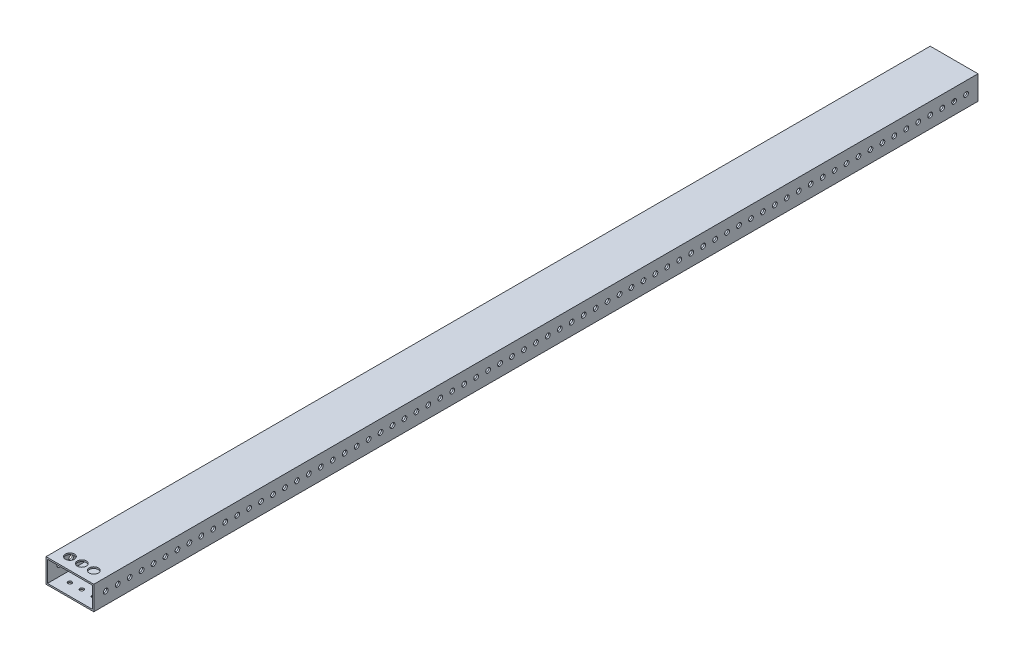
SolidWorks part; units mm, degrees
ref_plane "Front Plane" through (0, 0, 0) normal (0, 0, 1) x (1, 0, 0)
ref_plane "Top Plane" through (0, 0, 0) normal (0, 1, 0) x (1, 0, 0)
ref_plane "Right Plane" through (0, 0, 0) normal (1, 0, 0) x (0, 0, -1)
sketch "Sketch1" plane through (0, 0, 0) normal (0, 0, 1) x (1, 0, 0)
  line L0 (-23.8125, 11.1125) -> (23.8125, 11.1125)
  line L1 (-25.4, -12.7) -> (25.4, -12.7)
  line L2 (-25.4, -12.7) -> (-25.4, 12.7)
  line L3 (-25.4, 12.7) -> (25.4, 12.7)
  line L4 (25.4, -12.7) -> (25.4, 12.7)
  line L5 (-25.4, -12.7) -> (25.4, 12.7) construction
  line L6 (-25.4, 12.7) -> (25.4, -12.7) construction
  line L7 (23.8125, -11.1125) -> (23.8125, 11.1125)
  line L8 (-23.8125, -11.1125) -> (23.8125, -11.1125)
  line L9 (-23.8125, -11.1125) -> (-23.8125, 11.1125)
  point P0 (0, 0)
  dimension "D1" = 50.8
  dimension "D2" = 25.4
  dimension "D3" = 1.5875
extrude "Boss-Extrude1" add sketch "Sketch1" along normal mid plane 939.8
sketch "Sketch2" plane through (25.4, 0, 0) normal (1, 0, 0) x (0, 0, -1)
  line L0 (469.9, -12.7) -> (469.9, 12.7) construction
  line L1 (-469.9, -12.7) -> (-469.9, 12.7) construction
  line L2 (-469.9, 12.7) -> (469.9, 12.7) construction
  line L3 (-469.9, -12.7) -> (469.9, -12.7) construction
  circle A0 centre (457.2, 0) radius 2.54
  circle A1 centre (444.5, 0) radius 2.54
  circle A2 centre (431.8, 0) radius 2.54
  circle A3 centre (419.1, 0) radius 2.54
  circle A4 centre (406.4, 0) radius 2.54
  circle A5 centre (393.7, 0) radius 2.54
  circle A6 centre (381, 0) radius 2.54
  circle A7 centre (368.3, 0) radius 2.54
  circle A8 centre (355.6, 0) radius 2.54
  circle A9 centre (342.9, 0) radius 2.54
  circle A10 centre (330.2, 0) radius 2.54
  circle A11 centre (317.5, 0) radius 2.54
  circle A12 centre (304.8, 0) radius 2.54
  circle A13 centre (292.1, 0) radius 2.54
  circle A14 centre (279.4, 0) radius 2.54
  circle A15 centre (266.7, 0) radius 2.54
  circle A16 centre (254, 0) radius 2.54
  circle A17 centre (241.3, 0) radius 2.54
  circle A18 centre (228.6, 0) radius 2.54
  circle A19 centre (215.9, 0) radius 2.54
  circle A20 centre (203.2, 0) radius 2.54
  circle A21 centre (190.5, 0) radius 2.54
  circle A22 centre (177.8, 0) radius 2.54
  circle A23 centre (165.1, 0) radius 2.54
  circle A24 centre (152.4, 0) radius 2.54
  circle A25 centre (139.7, 0) radius 2.54
  circle A26 centre (127, 0) radius 2.54
  circle A27 centre (114.3, 0) radius 2.54
  circle A28 centre (101.6, 0) radius 2.54
  circle A29 centre (88.9, 0) radius 2.54
  circle A30 centre (76.2, 0) radius 2.54
  circle A31 centre (63.5, 0) radius 2.54
  circle A32 centre (50.8, 0) radius 2.54
  circle A33 centre (38.1, 0) radius 2.54
  circle A34 centre (25.4, 0) radius 2.54
  circle A35 centre (12.7, 0) radius 2.54
  circle A36 centre (0, 0) radius 2.54
  circle A37 centre (-12.7, 0) radius 2.54
  circle A38 centre (-25.4, 0) radius 2.54
  circle A39 centre (-38.1, 0) radius 2.54
  circle A40 centre (-50.8, 0) radius 2.54
  circle A41 centre (-63.5, 0) radius 2.54
  circle A42 centre (-76.2, 0) radius 2.54
  circle A43 centre (-88.9, 0) radius 2.54
  circle A44 centre (-101.6, 0) radius 2.54
  circle A45 centre (-114.3, 0) radius 2.54
  circle A46 centre (-127, 0) radius 2.54
  circle A47 centre (-139.7, 0) radius 2.54
  circle A48 centre (-152.4, 0) radius 2.54
  circle A49 centre (-165.1, 0) radius 2.54
  circle A50 centre (-177.8, 0) radius 2.54
  circle A51 centre (-190.5, 0) radius 2.54
  circle A52 centre (-203.2, 0) radius 2.54
  circle A53 centre (-215.9, 0) radius 2.54
  circle A54 centre (-228.6, 0) radius 2.54
  circle A55 centre (-241.3, 0) radius 2.54
  circle A56 centre (-254, 0) radius 2.54
  circle A57 centre (-266.7, 0) radius 2.54
  circle A58 centre (-279.4, 0) radius 2.54
  circle A59 centre (-292.1, 0) radius 2.54
  circle A60 centre (-304.8, 0) radius 2.54
  circle A61 centre (-317.5, 0) radius 2.54
  circle A62 centre (-330.2, 0) radius 2.54
  circle A63 centre (-342.9, 0) radius 2.54
  circle A64 centre (-355.6, 0) radius 2.54
  circle A65 centre (-368.3, 0) radius 2.54
  circle A66 centre (-381, 0) radius 2.54
  circle A67 centre (-393.7, 0) radius 2.54
  circle A68 centre (-406.4, 0) radius 2.54
  circle A69 centre (-419.1, 0) radius 2.54
  circle A70 centre (-431.8, 0) radius 2.54
  circle A71 centre (-444.5, 0) radius 2.54
  circle A72 centre (-457.2, 0) radius 2.54
  dimension "D2" = 5.08
  dimension "D1" = 12.7
  dimension "D4" = 12.7
  dimension "D5" = 12.7
  dimension "D6" = 12.7
  dimension "D3" = 73
extrude "Cut-Extrude1" cut sketch "Sketch2" against normal through all
sketch "Sketch4" plane through (0, 12.7, 0) normal (0, 1, 0) x (1, 0, 0)
  line L0 (25.4, -469.9) -> (-25.4, -469.9) construction
  circle A0 centre (-12.7, -457.2) radius 4.826
  circle A1 centre (0, -457.2) radius 4.826
  circle A2 centre (12.7, -457.2) radius 4.826
  point P6 (0, 0)
  point P7 (0, 0)
  point P9 (0, 0)
  dimension "D1" = 9.652
  dimension "D2" = 12.7
  dimension "D3" = 12.7
  dimension "D4" = 12.7
extrude "Cut-Extrude3" cut sketch "Sketch4" against normal up to surface (1.5875 mm away) contours A0 | A1 | A2 region at (-12.7, 12.7, 457.2) region at (0, 12.7, 457.2) region at (12.7, 12.7, 457.2) up to face at (0, 11.1125, 0)
sketch "Sketch5" plane through (0, -12.7, 0) normal (0, -1, 0) x (1, 0, 0)
  circle A0 centre (-12.7, 457.2) radius 4.826 construction
  circle A1 centre (0, 457.2) radius 4.826 construction
  circle A2 centre (12.7, 457.2) radius 4.826 construction
  circle A3 centre (-12.7, 457.2) radius 4.826
  circle A4 centre (0, 457.2) radius 4.826
  circle A5 centre (12.7, 457.2) radius 4.826
  circle A6 centre (-12.7, 457.2) radius 2.0193
  circle A7 centre (0, 457.2) radius 2.0193
  circle A8 centre (12.7, 457.2) radius 2.0193
  dimension "D1" = 4.0386
  dimension "D2" = 4.0386
  dimension "D3" = 4.0386
extrude "Cut-Extrude4" cut sketch "Sketch5" against normal up to surface (1.5875 mm away) contours A8 | A7 | A6 region at (-12.7, -12.7, 457.2) region at (0, -12.7, 457.2) region at (12.7, -12.7, 457.2) up to face at (0, -11.1125, 0)
sketch "Sketch6" plane through (0, -12.7, 0) normal (0, -1, 0) x (1, 0, 0)
  line L0 (-25.4, -469.9) -> (25.4, -469.9) construction
  circle A0 centre (-12.7, -457.2) radius 2.0193
  circle A1 centre (0, -457.2) radius 2.0193
  circle A2 centre (12.7, -457.2) radius 2.0193
  point P6 (0, 0)
  point P9 (0, 0)
  point P10 (0, 0)
  point P11 (0, 0)
  point P12 (0, 0)
  point P13 (0, 0)
  point P14 (0, 0)
  point P15 (0, 0)
  point P16 (0, 0)
  point P17 (0, 0)
  point P18 (0, 0)
  dimension "D1" = 4.0386
  dimension "D2" = 12.7
  dimension "D3" = 12.7
  dimension "D4" = 12.7
extrude "Cut-Extrude5" cut sketch "Sketch6" against normal up to surface (1.5875 mm away) contours A2 | A1 | A0 region at (-12.7, -12.7, -457.2) region at (0, -12.7, -457.2) region at (12.7, -12.7, -457.2) up to face at (12.7, -11.1125, 459.2193)
